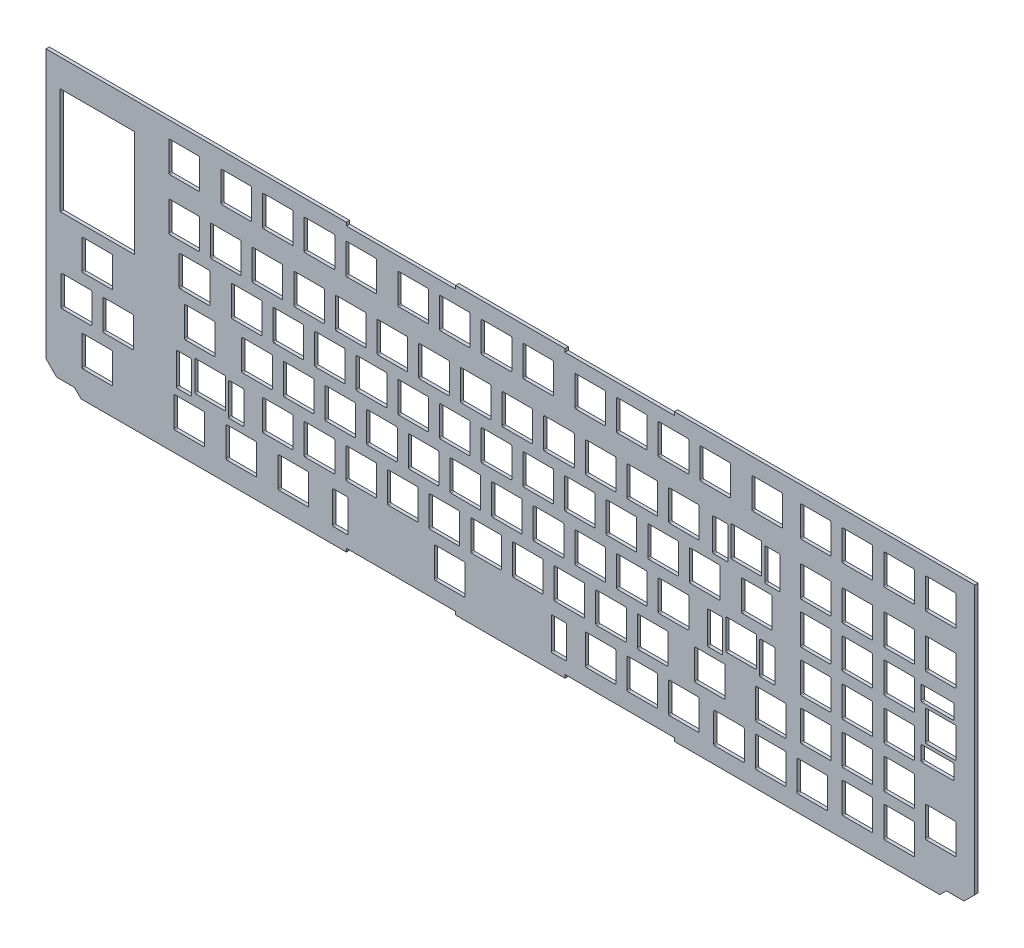
SolidWorks part; units mm, degrees
ref_plane "Přední rovina" through (0, 0, 0) normal (0, 0, 1) x (1, 0, 0)
ref_plane "Horní rovina" through (0, 0, 0) normal (0, 1, 0) x (1, 0, 0)
ref_plane "Pravá rovina" through (0, 0, 0) normal (1, 0, 0) x (0, 0, -1)
sketch "Model" plane through (0, 0, 0) normal (0, 0, 1) x (1, 0, 0)
  line L0 (53.8256, -2.525) -> (66.8256, -2.525)
  line L1 (53.8256, -16.525) -> (66.8256, -16.525)
  line L2 (53.3256, -3.025) -> (53.3256, -16.025)
  line L3 (67.3256, -3.025) -> (67.3256, -16.025)
  line L4 (77.6381, -2.525) -> (90.6381, -2.525)
  line L5 (77.6381, -16.525) -> (90.6381, -16.525)
  line L6 (77.1381, -3.025) -> (77.1381, -16.025)
  line L7 (91.1381, -3.025) -> (91.1381, -16.025)
  line L8 (96.6881, -2.525) -> (109.6881, -2.525)
  line L9 (96.6881, -16.525) -> (109.6881, -16.525)
  line L10 (96.1881, -3.025) -> (96.1881, -16.025)
  line L11 (110.1881, -3.025) -> (110.1881, -16.025)
  line L12 (115.7381, -2.525) -> (128.7381, -2.525)
  line L13 (115.7381, -16.525) -> (128.7381, -16.525)
  line L14 (115.2381, -3.025) -> (115.2381, -16.025)
  line L15 (129.2381, -3.025) -> (129.2381, -16.025)
  line L16 (134.7881, -2.525) -> (147.7881, -2.525)
  line L17 (134.7881, -16.525) -> (147.7881, -16.525)
  line L18 (134.2881, -3.025) -> (134.2881, -16.025)
  line L19 (148.2881, -3.025) -> (148.2881, -16.025)
  line L20 (158.6006, -2.525) -> (171.6006, -2.525)
  line L21 (158.6006, -16.525) -> (171.6006, -16.525)
  line L22 (158.1006, -3.025) -> (158.1006, -16.025)
  line L23 (172.1006, -3.025) -> (172.1006, -16.025)
  line L24 (177.6506, -2.525) -> (190.6506, -2.525)
  line L25 (177.6506, -16.525) -> (190.6506, -16.525)
  line L26 (177.1506, -3.025) -> (177.1506, -16.025)
  line L27 (191.1506, -3.025) -> (191.1506, -16.025)
  line L28 (196.7006, -2.525) -> (209.7006, -2.525)
  line L29 (196.7006, -16.525) -> (209.7006, -16.525)
  line L30 (196.2006, -3.025) -> (196.2006, -16.025)
  line L31 (210.2006, -3.025) -> (210.2006, -16.025)
  line L32 (215.7506, -2.525) -> (228.7506, -2.525)
  line L33 (215.7506, -16.525) -> (228.7506, -16.525)
  line L34 (215.2506, -3.025) -> (215.2506, -16.025)
  line L35 (229.2506, -3.025) -> (229.2506, -16.025)
  line L36 (239.5631, -2.525) -> (252.5631, -2.525)
  line L37 (239.5631, -16.525) -> (252.5631, -16.525)
  line L38 (239.0631, -3.025) -> (239.0631, -16.025)
  line L39 (253.0631, -3.025) -> (253.0631, -16.025)
  line L40 (258.6131, -2.525) -> (271.6131, -2.525)
  line L41 (258.6131, -16.525) -> (271.6131, -16.525)
  line L42 (258.1131, -3.025) -> (258.1131, -16.025)
  line L43 (272.1131, -3.025) -> (272.1131, -16.025)
  line L44 (277.6631, -2.525) -> (290.6631, -2.525)
  line L45 (277.6631, -16.525) -> (290.6631, -16.525)
  line L46 (277.1631, -3.025) -> (277.1631, -16.025)
  line L47 (291.1631, -3.025) -> (291.1631, -16.025)
  line L48 (296.7131, -2.525) -> (309.7131, -2.525)
  line L49 (296.7131, -16.525) -> (309.7131, -16.525)
  line L50 (296.2131, -3.025) -> (296.2131, -16.025)
  line L51 (310.2131, -3.025) -> (310.2131, -16.025)
  line L52 (320.5256, -2.525) -> (333.5256, -2.525)
  line L53 (320.5256, -16.525) -> (333.5256, -16.525)
  line L54 (320.0256, -3.025) -> (320.0256, -16.025)
  line L55 (334.0256, -3.025) -> (334.0256, -16.025)
  line L56 (342.7513, -2.525) -> (355.7513, -2.525)
  line L57 (342.7513, -16.525) -> (355.7513, -16.525)
  line L58 (342.2513, -3.025) -> (342.2513, -16.025)
  line L59 (356.2513, -3.025) -> (356.2513, -16.025)
  line L60 (361.8013, -2.525) -> (374.8013, -2.525)
  line L61 (361.8013, -16.525) -> (374.8013, -16.525)
  line L62 (361.3013, -3.025) -> (361.3013, -16.025)
  line L63 (375.3013, -3.025) -> (375.3013, -16.025)
  line L64 (380.8513, -2.525) -> (393.8513, -2.525)
  line L65 (380.8513, -16.525) -> (393.8513, -16.525)
  line L66 (380.3513, -3.025) -> (380.3513, -16.025)
  line L67 (394.3513, -3.025) -> (394.3513, -16.025)
  line L68 (399.9013, -2.525) -> (412.9013, -2.525)
  line L69 (399.9013, -16.525) -> (412.9013, -16.525)
  line L70 (399.4013, -3.025) -> (399.4013, -16.025)
  line L71 (413.4013, -3.025) -> (413.4013, -16.025)
  line L72 (53.8256, -26.3375) -> (66.8256, -26.3375)
  line L73 (53.8256, -40.3375) -> (66.8256, -40.3375)
  line L74 (53.3256, -26.8375) -> (53.3256, -39.8375)
  line L75 (67.3256, -26.8375) -> (67.3256, -39.8375)
  line L76 (72.8756, -26.3375) -> (85.8756, -26.3375)
  line L77 (72.8756, -40.3375) -> (85.8756, -40.3375)
  line L78 (72.3756, -26.8375) -> (72.3756, -39.8375)
  line L79 (86.3756, -26.8375) -> (86.3756, -39.8375)
  line L80 (91.9256, -26.3375) -> (104.9256, -26.3375)
  line L81 (91.9256, -40.3375) -> (104.9256, -40.3375)
  line L82 (91.4256, -26.8375) -> (91.4256, -39.8375)
  line L83 (105.4256, -26.8375) -> (105.4256, -39.8375)
  line L84 (110.9756, -26.3375) -> (123.9756, -26.3375)
  line L85 (110.9756, -40.3375) -> (123.9756, -40.3375)
  line L86 (110.4756, -26.8375) -> (110.4756, -39.8375)
  line L87 (124.4756, -26.8375) -> (124.4756, -39.8375)
  line L88 (130.0256, -26.3375) -> (143.0256, -26.3375)
  line L89 (130.0256, -40.3375) -> (143.0256, -40.3375)
  line L90 (129.5256, -26.8375) -> (129.5256, -39.8375)
  line L91 (143.5256, -26.8375) -> (143.5256, -39.8375)
  line L92 (149.0756, -26.3375) -> (162.0756, -26.3375)
  line L93 (149.0756, -40.3375) -> (162.0756, -40.3375)
  line L94 (148.5756, -26.8375) -> (148.5756, -39.8375)
  line L95 (162.5756, -26.8375) -> (162.5756, -39.8375)
  line L96 (168.1256, -26.3375) -> (181.1256, -26.3375)
  line L97 (168.1256, -40.3375) -> (181.1256, -40.3375)
  line L98 (167.6256, -26.8375) -> (167.6256, -39.8375)
  line L99 (181.6256, -26.8375) -> (181.6256, -39.8375)
  line L100 (187.1756, -26.3375) -> (200.1756, -26.3375)
  line L101 (187.1756, -40.3375) -> (200.1756, -40.3375)
  line L102 (186.6756, -26.8375) -> (186.6756, -39.8375)
  line L103 (200.6756, -26.8375) -> (200.6756, -39.8375)
  line L104 (206.2256, -26.3375) -> (219.2256, -26.3375)
  line L105 (206.2256, -40.3375) -> (219.2256, -40.3375)
  line L106 (205.7256, -26.8375) -> (205.7256, -39.8375)
  line L107 (219.7256, -26.8375) -> (219.7256, -39.8375)
  line L108 (225.2756, -26.3375) -> (238.2756, -26.3375)
  line L109 (225.2756, -40.3375) -> (238.2756, -40.3375)
  line L110 (224.7756, -26.8375) -> (224.7756, -39.8375)
  line L111 (238.7756, -26.8375) -> (238.7756, -39.8375)
  line L112 (244.3256, -26.3375) -> (257.3256, -26.3375)
  line L113 (244.3256, -40.3375) -> (257.3256, -40.3375)
  line L114 (243.8256, -26.8375) -> (243.8256, -39.8375)
  line L115 (257.8256, -26.8375) -> (257.8256, -39.8375)
  line L116 (263.3756, -26.3375) -> (276.3756, -26.3375)
  line L117 (263.3756, -40.3375) -> (276.3756, -40.3375)
  line L118 (262.8756, -26.8375) -> (262.8756, -39.8375)
  line L119 (276.8756, -26.8375) -> (276.8756, -39.8375)
  line L120 (282.4256, -26.3375) -> (295.4256, -26.3375)
  line L121 (282.4256, -40.3375) -> (295.4256, -40.3375)
  line L122 (281.9256, -26.8375) -> (281.9256, -39.8375)
  line L123 (295.9256, -26.8375) -> (295.9256, -39.8375)
  line L124 (311.0006, -26.3375) -> (324.0006, -26.3375)
  line L125 (311.0006, -40.3375) -> (324.0006, -40.3375)
  line L126 (310.5006, -26.8375) -> (310.5006, -39.8375)
  line L127 (324.5006, -26.8375) -> (324.5006, -39.8375)
  line L128 (302.5626, -27.3375) -> (308.5626, -27.3375)
  line L129 (302.5626, -42.3375) -> (308.5626, -42.3375)
  line L130 (302.0626, -27.8375) -> (302.0626, -41.8375)
  line L131 (309.0626, -27.8375) -> (309.0626, -41.8375)
  line L132 (326.4386, -27.3375) -> (332.4386, -27.3375)
  line L133 (326.4386, -42.3375) -> (332.4386, -42.3375)
  line L134 (325.9386, -27.8375) -> (325.9386, -41.8375)
  line L135 (332.9386, -27.8375) -> (332.9386, -41.8375)
  line L136 (342.7513, -26.3375) -> (355.7513, -26.3375)
  line L137 (342.7513, -40.3375) -> (355.7513, -40.3375)
  line L138 (342.2513, -26.8375) -> (342.2513, -39.8375)
  line L139 (356.2513, -26.8375) -> (356.2513, -39.8375)
  line L140 (361.8013, -26.3375) -> (374.8013, -26.3375)
  line L141 (361.8013, -40.3375) -> (374.8013, -40.3375)
  line L142 (361.3013, -26.8375) -> (361.3013, -39.8375)
  line L143 (375.3013, -26.8375) -> (375.3013, -39.8375)
  line L144 (380.8513, -26.3375) -> (393.8513, -26.3375)
  line L145 (380.8513, -40.3375) -> (393.8513, -40.3375)
  line L146 (380.3513, -26.8375) -> (380.3513, -39.8375)
  line L147 (394.3513, -26.8375) -> (394.3513, -39.8375)
  line L148 (399.9013, -26.3375) -> (412.9013, -26.3375)
  line L149 (399.9013, -40.3375) -> (412.9013, -40.3375)
  line L150 (399.4013, -26.8375) -> (399.4013, -39.8375)
  line L151 (413.4013, -26.8375) -> (413.4013, -39.8375)
  line L152 (58.5881, -45.3875) -> (71.5881, -45.3875)
  line L153 (58.5881, -59.3875) -> (71.5881, -59.3875)
  line L154 (58.0881, -45.8875) -> (58.0881, -58.8875)
  line L155 (72.0881, -45.8875) -> (72.0881, -58.8875)
  line L156 (82.4006, -45.3875) -> (95.4006, -45.3875)
  line L157 (82.4006, -59.3875) -> (95.4006, -59.3875)
  line L158 (81.9006, -45.8875) -> (81.9006, -58.8875)
  line L159 (95.9006, -45.8875) -> (95.9006, -58.8875)
  line L160 (101.4506, -45.3875) -> (114.4506, -45.3875)
  line L161 (101.4506, -59.3875) -> (114.4506, -59.3875)
  line L162 (100.9506, -45.8875) -> (100.9506, -58.8875)
  line L163 (114.9506, -45.8875) -> (114.9506, -58.8875)
  line L164 (120.5006, -45.3875) -> (133.5006, -45.3875)
  line L165 (120.5006, -59.3875) -> (133.5006, -59.3875)
  line L166 (120.0006, -45.8875) -> (120.0006, -58.8875)
  line L167 (134.0006, -45.8875) -> (134.0006, -58.8875)
  line L168 (139.5506, -45.3875) -> (152.5506, -45.3875)
  line L169 (139.5506, -59.3875) -> (152.5506, -59.3875)
  line L170 (139.0506, -45.8875) -> (139.0506, -58.8875)
  line L171 (153.0506, -45.8875) -> (153.0506, -58.8875)
  line L172 (158.6006, -45.3875) -> (171.6006, -45.3875)
  line L173 (158.6006, -59.3875) -> (171.6006, -59.3875)
  line L174 (158.1006, -45.8875) -> (158.1006, -58.8875)
  line L175 (172.1006, -45.8875) -> (172.1006, -58.8875)
  line L176 (177.6506, -45.3875) -> (190.6506, -45.3875)
  line L177 (177.6506, -59.3875) -> (190.6506, -59.3875)
  line L178 (177.1506, -45.8875) -> (177.1506, -58.8875)
  line L179 (191.1506, -45.8875) -> (191.1506, -58.8875)
  line L180 (196.7006, -45.3875) -> (209.7006, -45.3875)
  line L181 (196.7006, -59.3875) -> (209.7006, -59.3875)
  line L182 (196.2006, -45.8875) -> (196.2006, -58.8875)
  line L183 (210.2006, -45.8875) -> (210.2006, -58.8875)
  line L184 (215.7506, -45.3875) -> (228.7506, -45.3875)
  line L185 (215.7506, -59.3875) -> (228.7506, -59.3875)
  line L186 (215.2506, -45.8875) -> (215.2506, -58.8875)
  line L187 (229.2506, -45.8875) -> (229.2506, -58.8875)
  line L188 (234.8006, -45.3875) -> (247.8006, -45.3875)
  line L189 (234.8006, -59.3875) -> (247.8006, -59.3875)
  line L190 (234.3006, -45.8875) -> (234.3006, -58.8875)
  line L191 (248.3006, -45.8875) -> (248.3006, -58.8875)
  line L192 (253.8506, -45.3875) -> (266.8506, -45.3875)
  line L193 (253.8506, -59.3875) -> (266.8506, -59.3875)
  line L194 (253.3506, -45.8875) -> (253.3506, -58.8875)
  line L195 (267.3506, -45.8875) -> (267.3506, -58.8875)
  line L196 (272.9006, -45.3875) -> (285.9006, -45.3875)
  line L197 (272.9006, -59.3875) -> (285.9006, -59.3875)
  line L198 (272.4006, -45.8875) -> (272.4006, -58.8875)
  line L199 (286.4006, -45.8875) -> (286.4006, -58.8875)
  line L200 (291.9506, -45.3875) -> (304.9506, -45.3875)
  line L201 (291.9506, -59.3875) -> (304.9506, -59.3875)
  line L202 (291.4506, -45.8875) -> (291.4506, -58.8875)
  line L203 (305.4506, -45.8875) -> (305.4506, -58.8875)
  line L204 (315.7631, -45.3875) -> (328.7631, -45.3875)
  line L205 (315.7631, -59.3875) -> (328.7631, -59.3875)
  line L206 (315.2631, -45.8875) -> (315.2631, -58.8875)
  line L207 (329.2631, -45.8875) -> (329.2631, -58.8875)
  line L208 (342.7513, -45.3875) -> (355.7513, -45.3875)
  line L209 (342.7513, -59.3875) -> (355.7513, -59.3875)
  line L210 (342.2513, -45.8875) -> (342.2513, -58.8875)
  line L211 (356.2513, -45.8875) -> (356.2513, -58.8875)
  line L212 (361.8013, -45.3875) -> (374.8013, -45.3875)
  line L213 (361.8013, -59.3875) -> (374.8013, -59.3875)
  line L214 (361.3013, -45.8875) -> (361.3013, -58.8875)
  line L215 (375.3013, -45.8875) -> (375.3013, -58.8875)
  line L216 (380.8513, -45.3875) -> (393.8513, -45.3875)
  line L217 (380.8513, -59.3875) -> (393.8513, -59.3875)
  line L218 (380.3513, -45.8875) -> (380.3513, -58.8875)
  line L219 (394.3513, -45.8875) -> (394.3513, -58.8875)
  line L220 (413.4013, -55.4125) -> (413.4013, -68.4125)
  line L221 (399.4013, -55.4125) -> (399.4013, -68.4125)
  line L222 (412.9013, -54.9125) -> (399.9013, -54.9125)
  line L223 (412.9013, -68.9125) -> (399.9013, -68.9125)
  line L224 (412.4013, -46.9745) -> (412.4013, -52.9745)
  line L225 (397.4013, -46.9745) -> (397.4013, -52.9745)
  line L226 (411.9013, -46.4745) -> (397.9013, -46.4745)
  line L227 (411.9013, -53.4745) -> (397.9013, -53.4745)
  line L228 (412.4013, -70.8505) -> (412.4013, -76.8505)
  line L229 (397.4013, -70.8505) -> (397.4013, -76.8505)
  line L230 (411.9013, -70.3505) -> (397.9013, -70.3505)
  line L231 (411.9013, -77.3505) -> (397.9013, -77.3505)
  line L232 (14.1369, -61.2619) -> (27.1369, -61.2619)
  line L233 (14.1369, -75.2619) -> (27.1369, -75.2619)
  line L234 (13.6369, -61.7619) -> (13.6369, -74.7619)
  line L235 (27.6369, -61.7619) -> (27.6369, -74.7619)
  line L236 (60.9694, -64.4375) -> (73.9694, -64.4375)
  line L237 (60.9694, -78.4375) -> (73.9694, -78.4375)
  line L238 (60.4694, -64.9375) -> (60.4694, -77.9375)
  line L239 (74.4694, -64.9375) -> (74.4694, -77.9375)
  line L240 (87.1631, -64.4375) -> (100.1631, -64.4375)
  line L241 (87.1631, -78.4375) -> (100.1631, -78.4375)
  line L242 (86.6631, -64.9375) -> (86.6631, -77.9375)
  line L243 (100.6631, -64.9375) -> (100.6631, -77.9375)
  line L244 (106.2131, -64.4375) -> (119.2131, -64.4375)
  line L245 (106.2131, -78.4375) -> (119.2131, -78.4375)
  line L246 (105.7131, -64.9375) -> (105.7131, -77.9375)
  line L247 (119.7131, -64.9375) -> (119.7131, -77.9375)
  line L248 (125.2631, -64.4375) -> (138.2631, -64.4375)
  line L249 (125.2631, -78.4375) -> (138.2631, -78.4375)
  line L250 (124.7631, -64.9375) -> (124.7631, -77.9375)
  line L251 (138.7631, -64.9375) -> (138.7631, -77.9375)
  line L252 (144.3131, -64.4375) -> (157.3131, -64.4375)
  line L253 (144.3131, -78.4375) -> (157.3131, -78.4375)
  line L254 (143.8131, -64.9375) -> (143.8131, -77.9375)
  line L255 (157.8131, -64.9375) -> (157.8131, -77.9375)
  line L256 (163.3631, -64.4375) -> (176.3631, -64.4375)
  line L257 (163.3631, -78.4375) -> (176.3631, -78.4375)
  line L258 (162.8631, -64.9375) -> (162.8631, -77.9375)
  line L259 (176.8631, -64.9375) -> (176.8631, -77.9375)
  line L260 (182.4131, -64.4375) -> (195.4131, -64.4375)
  line L261 (182.4131, -78.4375) -> (195.4131, -78.4375)
  line L262 (181.9131, -64.9375) -> (181.9131, -77.9375)
  line L263 (195.9131, -64.9375) -> (195.9131, -77.9375)
  line L264 (201.4631, -64.4375) -> (214.4631, -64.4375)
  line L265 (201.4631, -78.4375) -> (214.4631, -78.4375)
  line L266 (200.9631, -64.9375) -> (200.9631, -77.9375)
  line L267 (214.9631, -64.9375) -> (214.9631, -77.9375)
  line L268 (220.5131, -64.4375) -> (233.5131, -64.4375)
  line L269 (220.5131, -78.4375) -> (233.5131, -78.4375)
  line L270 (220.0131, -64.9375) -> (220.0131, -77.9375)
  line L271 (234.0131, -64.9375) -> (234.0131, -77.9375)
  line L272 (239.5631, -64.4375) -> (252.5631, -64.4375)
  line L273 (239.5631, -78.4375) -> (252.5631, -78.4375)
  line L274 (239.0631, -64.9375) -> (239.0631, -77.9375)
  line L275 (253.0631, -64.9375) -> (253.0631, -77.9375)
  line L276 (258.6131, -64.4375) -> (271.6131, -64.4375)
  line L277 (258.6131, -78.4375) -> (271.6131, -78.4375)
  line L278 (258.1131, -64.9375) -> (258.1131, -77.9375)
  line L279 (272.1131, -64.9375) -> (272.1131, -77.9375)
  line L280 (277.6631, -64.4375) -> (290.6631, -64.4375)
  line L281 (277.6631, -78.4375) -> (290.6631, -78.4375)
  line L282 (277.1631, -64.9375) -> (277.1631, -77.9375)
  line L283 (291.1631, -64.9375) -> (291.1631, -77.9375)
  line L284 (308.6194, -64.4375) -> (321.6194, -64.4375)
  line L285 (308.6194, -78.4375) -> (321.6194, -78.4375)
  line L286 (308.1194, -64.9375) -> (308.1194, -77.9375)
  line L287 (322.1194, -64.9375) -> (322.1194, -77.9375)
  line L288 (300.1814, -65.4375) -> (306.1814, -65.4375)
  line L289 (300.1814, -80.4375) -> (306.1814, -80.4375)
  line L290 (299.6814, -65.9375) -> (299.6814, -79.9375)
  line L291 (306.6814, -65.9375) -> (306.6814, -79.9375)
  line L292 (324.0574, -65.4375) -> (330.0574, -65.4375)
  line L293 (324.0574, -80.4375) -> (330.0574, -80.4375)
  line L294 (323.5574, -65.9375) -> (323.5574, -79.9375)
  line L295 (330.5574, -65.9375) -> (330.5574, -79.9375)
  line L296 (342.7513, -64.4375) -> (355.7513, -64.4375)
  line L297 (342.7513, -78.4375) -> (355.7513, -78.4375)
  line L298 (342.2513, -64.9375) -> (342.2513, -77.9375)
  line L299 (356.2513, -64.9375) -> (356.2513, -77.9375)
  line L300 (361.8013, -64.4375) -> (374.8013, -64.4375)
  line L301 (361.8013, -78.4375) -> (374.8013, -78.4375)
  line L302 (361.3013, -64.9375) -> (361.3013, -77.9375)
  line L303 (375.3013, -64.9375) -> (375.3013, -77.9375)
  line L304 (380.8513, -64.4375) -> (393.8513, -64.4375)
  line L305 (380.8513, -78.4375) -> (393.8513, -78.4375)
  line L306 (380.3513, -64.9375) -> (380.3513, -77.9375)
  line L307 (394.3513, -64.9375) -> (394.3513, -77.9375)
  line L308 (4.6119, -80.3119) -> (17.6119, -80.3119)
  line L309 (4.6119, -94.3119) -> (17.6119, -94.3119)
  line L310 (4.1119, -80.8119) -> (4.1119, -93.8119)
  line L311 (18.1119, -80.8119) -> (18.1119, -93.8119)
  line L312 (23.6619, -80.3119) -> (36.6619, -80.3119)
  line L313 (23.6619, -94.3119) -> (36.6619, -94.3119)
  line L314 (23.1619, -80.8119) -> (23.1619, -93.8119)
  line L315 (37.1619, -80.8119) -> (37.1619, -93.8119)
  line L316 (65.7319, -83.4875) -> (78.7319, -83.4875)
  line L317 (65.7319, -97.4875) -> (78.7319, -97.4875)
  line L318 (65.2319, -83.9875) -> (65.2319, -96.9875)
  line L319 (79.2319, -83.9875) -> (79.2319, -96.9875)
  line L320 (57.2939, -84.4875) -> (63.2939, -84.4875)
  line L321 (57.2939, -99.4875) -> (63.2939, -99.4875)
  line L322 (56.7939, -84.9875) -> (56.7939, -98.9875)
  line L323 (63.7939, -84.9875) -> (63.7939, -98.9875)
  line L324 (81.1699, -84.4875) -> (87.1699, -84.4875)
  line L325 (81.1699, -99.4875) -> (87.1699, -99.4875)
  line L326 (80.6699, -84.9875) -> (80.6699, -98.9875)
  line L327 (87.6699, -84.9875) -> (87.6699, -98.9875)
  line L328 (96.6881, -83.4875) -> (109.6881, -83.4875)
  line L329 (96.6881, -97.4875) -> (109.6881, -97.4875)
  line L330 (96.1881, -83.9875) -> (96.1881, -96.9875)
  line L331 (110.1881, -83.9875) -> (110.1881, -96.9875)
  line L332 (115.7381, -83.4875) -> (128.7381, -83.4875)
  line L333 (115.7381, -97.4875) -> (128.7381, -97.4875)
  line L334 (115.2381, -83.9875) -> (115.2381, -96.9875)
  line L335 (129.2381, -83.9875) -> (129.2381, -96.9875)
  line L336 (134.7881, -83.4875) -> (147.7881, -83.4875)
  line L337 (134.7881, -97.4875) -> (147.7881, -97.4875)
  line L338 (134.2881, -83.9875) -> (134.2881, -96.9875)
  line L339 (148.2881, -83.9875) -> (148.2881, -96.9875)
  line L340 (153.8381, -83.4875) -> (166.8381, -83.4875)
  line L341 (153.8381, -97.4875) -> (166.8381, -97.4875)
  line L342 (153.3381, -83.9875) -> (153.3381, -96.9875)
  line L343 (167.3381, -83.9875) -> (167.3381, -96.9875)
  line L344 (172.8881, -83.4875) -> (185.8881, -83.4875)
  line L345 (172.8881, -97.4875) -> (185.8881, -97.4875)
  line L346 (172.3881, -83.9875) -> (172.3881, -96.9875)
  line L347 (186.3881, -83.9875) -> (186.3881, -96.9875)
  line L348 (191.9381, -83.4875) -> (204.9381, -83.4875)
  line L349 (191.9381, -97.4875) -> (204.9381, -97.4875)
  line L350 (191.4381, -83.9875) -> (191.4381, -96.9875)
  line L351 (205.4381, -83.9875) -> (205.4381, -96.9875)
  line L352 (210.9881, -83.4875) -> (223.9881, -83.4875)
  line L353 (210.9881, -97.4875) -> (223.9881, -97.4875)
  line L354 (210.4881, -83.9875) -> (210.4881, -96.9875)
  line L355 (224.4881, -83.9875) -> (224.4881, -96.9875)
  line L356 (230.0381, -83.4875) -> (243.0381, -83.4875)
  line L357 (230.0381, -97.4875) -> (243.0381, -97.4875)
  line L358 (229.5381, -83.9875) -> (229.5381, -96.9875)
  line L359 (243.5381, -83.9875) -> (243.5381, -96.9875)
  line L360 (249.0881, -83.4875) -> (262.0881, -83.4875)
  line L361 (249.0881, -97.4875) -> (262.0881, -97.4875)
  line L362 (248.5881, -83.9875) -> (248.5881, -96.9875)
  line L363 (262.5881, -83.9875) -> (262.5881, -96.9875)
  line L364 (268.1381, -83.4875) -> (281.1381, -83.4875)
  line L365 (268.1381, -97.4875) -> (281.1381, -97.4875)
  line L366 (267.6381, -83.9875) -> (267.6381, -96.9875)
  line L367 (281.6381, -83.9875) -> (281.6381, -96.9875)
  line L368 (294.3319, -83.4875) -> (307.3319, -83.4875)
  line L369 (294.3319, -97.4875) -> (307.3319, -97.4875)
  line L370 (293.8319, -83.9875) -> (293.8319, -96.9875)
  line L371 (307.8319, -83.9875) -> (307.8319, -96.9875)
  line L372 (342.7513, -83.4875) -> (355.7513, -83.4875)
  line L373 (342.7513, -97.4875) -> (355.7513, -97.4875)
  line L374 (342.2513, -83.9875) -> (342.2513, -96.9875)
  line L375 (356.2513, -83.9875) -> (356.2513, -96.9875)
  line L376 (361.8013, -83.4875) -> (374.8013, -83.4875)
  line L377 (361.8013, -97.4875) -> (374.8013, -97.4875)
  line L378 (361.3013, -83.9875) -> (361.3013, -96.9875)
  line L379 (375.3013, -83.9875) -> (375.3013, -96.9875)
  line L380 (380.8513, -83.4875) -> (393.8513, -83.4875)
  line L381 (380.8513, -97.4875) -> (393.8513, -97.4875)
  line L382 (380.3513, -83.9875) -> (380.3513, -96.9875)
  line L383 (394.3513, -83.9875) -> (394.3513, -96.9875)
  line L384 (413.4013, -93.5125) -> (413.4013, -106.5125)
  line L385 (399.4013, -93.5125) -> (399.4013, -106.5125)
  line L386 (412.9013, -93.0125) -> (399.9013, -93.0125)
  line L387 (412.9013, -107.0125) -> (399.9013, -107.0125)
  line L396 (322.1125, -85.0744) -> (335.1125, -85.0744)
  line L397 (322.1125, -99.0744) -> (335.1125, -99.0744)
  line L398 (321.6125, -85.5744) -> (321.6125, -98.5744)
  line L399 (335.6125, -85.5744) -> (335.6125, -98.5744)
  line L400 (14.1369, -99.3619) -> (27.1369, -99.3619)
  line L401 (14.1369, -113.3619) -> (27.1369, -113.3619)
  line L402 (13.6369, -99.8619) -> (13.6369, -112.8619)
  line L403 (27.6369, -99.8619) -> (27.6369, -112.8619)
  line L404 (56.2069, -102.5375) -> (69.2069, -102.5375)
  line L405 (56.2069, -116.5375) -> (69.2069, -116.5375)
  line L406 (55.7069, -103.0375) -> (55.7069, -116.0375)
  line L407 (69.7069, -103.0375) -> (69.7069, -116.0375)
  line L408 (80.0194, -102.5375) -> (93.0194, -102.5375)
  line L409 (80.0194, -116.5375) -> (93.0194, -116.5375)
  line L410 (79.5194, -103.0375) -> (79.5194, -116.0375)
  line L411 (93.5194, -103.0375) -> (93.5194, -116.0375)
  line L412 (103.8319, -102.5375) -> (116.8319, -102.5375)
  line L413 (103.8319, -116.5375) -> (116.8319, -116.5375)
  line L414 (103.3319, -103.0375) -> (103.3319, -116.0375)
  line L415 (117.3319, -103.0375) -> (117.3319, -116.0375)
  line L416 (175.2694, -102.5375) -> (188.2694, -102.5375)
  line L417 (175.2694, -116.5375) -> (188.2694, -116.5375)
  line L418 (174.7694, -103.0375) -> (174.7694, -116.0375)
  line L419 (188.7694, -103.0375) -> (188.7694, -116.0375)
  line L420 (128.7694, -103.5375) -> (134.7694, -103.5375)
  line L421 (128.7694, -118.5375) -> (134.7694, -118.5375)
  line L422 (128.2694, -104.0375) -> (128.2694, -118.0375)
  line L423 (135.2694, -104.0375) -> (135.2694, -118.0375)
  line L424 (228.7694, -103.5375) -> (234.7694, -103.5375)
  line L425 (228.7694, -118.5375) -> (234.7694, -118.5375)
  line L426 (228.2694, -104.0375) -> (228.2694, -118.0375)
  line L427 (235.2694, -104.0375) -> (235.2694, -118.0375)
  line L428 (244.3256, -102.5375) -> (257.3256, -102.5375)
  line L429 (244.3256, -116.5375) -> (257.3256, -116.5375)
  line L430 (243.8256, -103.0375) -> (243.8256, -116.0375)
  line L431 (257.8256, -103.0375) -> (257.8256, -116.0375)
  line L432 (263.3756, -102.5375) -> (276.3756, -102.5375)
  line L433 (263.3756, -116.5375) -> (276.3756, -116.5375)
  line L434 (262.8756, -103.0375) -> (262.8756, -116.0375)
  line L435 (276.8756, -103.0375) -> (276.8756, -116.0375)
  line L436 (282.4256, -102.5375) -> (295.4256, -102.5375)
  line L437 (282.4256, -116.5375) -> (295.4256, -116.5375)
  line L438 (281.9256, -103.0375) -> (281.9256, -116.0375)
  line L439 (295.9256, -103.0375) -> (295.9256, -116.0375)
  line L440 (361.8013, -102.5375) -> (374.8013, -102.5375)
  line L441 (361.8013, -116.5375) -> (374.8013, -116.5375)
  line L442 (361.3013, -103.0375) -> (361.3013, -116.0375)
  line L443 (375.3013, -103.0375) -> (375.3013, -116.0375)
  line L444 (380.8513, -102.5375) -> (393.8513, -102.5375)
  line L445 (380.8513, -116.5375) -> (393.8513, -116.5375)
  line L446 (380.3513, -103.0375) -> (380.3513, -116.0375)
  line L447 (394.3513, -103.0375) -> (394.3513, -116.0375)
  line L448 (303.0625, -104.1244) -> (316.0625, -104.1244)
  line L449 (303.0625, -118.1244) -> (316.0625, -118.1244)
  line L450 (302.5625, -104.6244) -> (302.5625, -117.6244)
  line L451 (316.5625, -104.6244) -> (316.5625, -117.6244)
  line L452 (322.1125, -104.1244) -> (335.1125, -104.1244)
  line L453 (322.1125, -118.1244) -> (335.1125, -118.1244)
  line L454 (321.6125, -104.6244) -> (321.6125, -117.6244)
  line L455 (335.6125, -104.6244) -> (335.6125, -117.6244)
  line L456 (341.1625, -104.1244) -> (354.1625, -104.1244)
  line L457 (341.1625, -118.1244) -> (354.1625, -118.1244)
  line L458 (340.6625, -104.6244) -> (340.6625, -117.6244)
  line L459 (354.6625, -104.6244) -> (354.6625, -117.6244)
  line L460 (1.5869, -120.6494) -> (417.5131, -120.6494)
  line L461 (1.5869, 0) -> (417.5131, 0)
  line L462 (1.5869, -120.6494) -> (1.5869, 0)
  line L463 (417.5131, -120.6494) -> (417.5131, 0)
  arc A0 (53.8256, -2.525) -> (53.3256, -3.025) centre (53.8256, -3.025) ccw
  arc A1 (67.3256, -3.025) -> (66.8256, -2.525) centre (66.8256, -3.025) ccw
  arc A2 (53.3256, -16.025) -> (53.8256, -16.525) centre (53.8256, -16.025) ccw
  arc A3 (66.8256, -16.525) -> (67.3256, -16.025) centre (66.8256, -16.025) ccw
  arc A4 (77.6381, -2.525) -> (77.1381, -3.025) centre (77.6381, -3.025) ccw
  arc A5 (91.1381, -3.025) -> (90.6381, -2.525) centre (90.6381, -3.025) ccw
  arc A6 (77.1381, -16.025) -> (77.6381, -16.525) centre (77.6381, -16.025) ccw
  arc A7 (90.6381, -16.525) -> (91.1381, -16.025) centre (90.6381, -16.025) ccw
  arc A8 (96.6881, -2.525) -> (96.1881, -3.025) centre (96.6881, -3.025) ccw
  arc A9 (110.1881, -3.025) -> (109.6881, -2.525) centre (109.6881, -3.025) ccw
  arc A10 (96.1881, -16.025) -> (96.6881, -16.525) centre (96.6881, -16.025) ccw
  arc A11 (109.6881, -16.525) -> (110.1881, -16.025) centre (109.6881, -16.025) ccw
  arc A12 (115.7381, -2.525) -> (115.2381, -3.025) centre (115.7381, -3.025) ccw
  arc A13 (129.2381, -3.025) -> (128.7381, -2.525) centre (128.7381, -3.025) ccw
  arc A14 (115.2381, -16.025) -> (115.7381, -16.525) centre (115.7381, -16.025) ccw
  arc A15 (128.7381, -16.525) -> (129.2381, -16.025) centre (128.7381, -16.025) ccw
  arc A16 (134.7881, -2.525) -> (134.2881, -3.025) centre (134.7881, -3.025) ccw
  arc A17 (148.2881, -3.025) -> (147.7881, -2.525) centre (147.7881, -3.025) ccw
  arc A18 (134.2881, -16.025) -> (134.7881, -16.525) centre (134.7881, -16.025) ccw
  arc A19 (147.7881, -16.525) -> (148.2881, -16.025) centre (147.7881, -16.025) ccw
  arc A20 (158.6006, -2.525) -> (158.1006, -3.025) centre (158.6006, -3.025) ccw
  arc A21 (172.1006, -3.025) -> (171.6006, -2.525) centre (171.6006, -3.025) ccw
  arc A22 (158.1006, -16.025) -> (158.6006, -16.525) centre (158.6006, -16.025) ccw
  arc A23 (171.6006, -16.525) -> (172.1006, -16.025) centre (171.6006, -16.025) ccw
  arc A24 (177.6506, -2.525) -> (177.1506, -3.025) centre (177.6506, -3.025) ccw
  arc A25 (191.1506, -3.025) -> (190.6506, -2.525) centre (190.6506, -3.025) ccw
  arc A26 (177.1506, -16.025) -> (177.6506, -16.525) centre (177.6506, -16.025) ccw
  arc A27 (190.6506, -16.525) -> (191.1506, -16.025) centre (190.6506, -16.025) ccw
  arc A28 (196.7006, -2.525) -> (196.2006, -3.025) centre (196.7006, -3.025) ccw
  arc A29 (210.2006, -3.025) -> (209.7006, -2.525) centre (209.7006, -3.025) ccw
  arc A30 (196.2006, -16.025) -> (196.7006, -16.525) centre (196.7006, -16.025) ccw
  arc A31 (209.7006, -16.525) -> (210.2006, -16.025) centre (209.7006, -16.025) ccw
  arc A32 (215.7506, -2.525) -> (215.2506, -3.025) centre (215.7506, -3.025) ccw
  arc A33 (229.2506, -3.025) -> (228.7506, -2.525) centre (228.7506, -3.025) ccw
  arc A34 (215.2506, -16.025) -> (215.7506, -16.525) centre (215.7506, -16.025) ccw
  arc A35 (228.7506, -16.525) -> (229.2506, -16.025) centre (228.7506, -16.025) ccw
  arc A36 (239.5631, -2.525) -> (239.0631, -3.025) centre (239.5631, -3.025) ccw
  arc A37 (253.0631, -3.025) -> (252.5631, -2.525) centre (252.5631, -3.025) ccw
  arc A38 (239.0631, -16.025) -> (239.5631, -16.525) centre (239.5631, -16.025) ccw
  arc A39 (252.5631, -16.525) -> (253.0631, -16.025) centre (252.5631, -16.025) ccw
  arc A40 (258.6131, -2.525) -> (258.1131, -3.025) centre (258.6131, -3.025) ccw
  arc A41 (272.1131, -3.025) -> (271.6131, -2.525) centre (271.6131, -3.025) ccw
  arc A42 (258.1131, -16.025) -> (258.6131, -16.525) centre (258.6131, -16.025) ccw
  arc A43 (271.6131, -16.525) -> (272.1131, -16.025) centre (271.6131, -16.025) ccw
  arc A44 (277.6631, -2.525) -> (277.1631, -3.025) centre (277.6631, -3.025) ccw
  arc A45 (291.1631, -3.025) -> (290.6631, -2.525) centre (290.6631, -3.025) ccw
  arc A46 (277.1631, -16.025) -> (277.6631, -16.525) centre (277.6631, -16.025) ccw
  arc A47 (290.6631, -16.525) -> (291.1631, -16.025) centre (290.6631, -16.025) ccw
  arc A48 (296.7131, -2.525) -> (296.2131, -3.025) centre (296.7131, -3.025) ccw
  arc A49 (310.2131, -3.025) -> (309.7131, -2.525) centre (309.7131, -3.025) ccw
  arc A50 (296.2131, -16.025) -> (296.7131, -16.525) centre (296.7131, -16.025) ccw
  arc A51 (309.7131, -16.525) -> (310.2131, -16.025) centre (309.7131, -16.025) ccw
  arc A52 (320.5256, -2.525) -> (320.0256, -3.025) centre (320.5256, -3.025) ccw
  arc A53 (334.0256, -3.025) -> (333.5256, -2.525) centre (333.5256, -3.025) ccw
  arc A54 (320.0256, -16.025) -> (320.5256, -16.525) centre (320.5256, -16.025) ccw
  arc A55 (333.5256, -16.525) -> (334.0256, -16.025) centre (333.5256, -16.025) ccw
  arc A56 (342.7513, -2.525) -> (342.2513, -3.025) centre (342.7513, -3.025) ccw
  arc A57 (356.2513, -3.025) -> (355.7513, -2.525) centre (355.7513, -3.025) ccw
  arc A58 (342.2513, -16.025) -> (342.7513, -16.525) centre (342.7513, -16.025) ccw
  arc A59 (355.7513, -16.525) -> (356.2513, -16.025) centre (355.7513, -16.025) ccw
  arc A60 (361.8013, -2.525) -> (361.3013, -3.025) centre (361.8013, -3.025) ccw
  arc A61 (375.3013, -3.025) -> (374.8013, -2.525) centre (374.8013, -3.025) ccw
  arc A62 (361.3013, -16.025) -> (361.8013, -16.525) centre (361.8013, -16.025) ccw
  arc A63 (374.8013, -16.525) -> (375.3013, -16.025) centre (374.8013, -16.025) ccw
  arc A64 (380.8513, -2.525) -> (380.3513, -3.025) centre (380.8513, -3.025) ccw
  arc A65 (394.3513, -3.025) -> (393.8513, -2.525) centre (393.8513, -3.025) ccw
  arc A66 (380.3513, -16.025) -> (380.8513, -16.525) centre (380.8513, -16.025) ccw
  arc A67 (393.8513, -16.525) -> (394.3513, -16.025) centre (393.8513, -16.025) ccw
  arc A68 (399.9013, -2.525) -> (399.4013, -3.025) centre (399.9013, -3.025) ccw
  arc A69 (413.4013, -3.025) -> (412.9013, -2.525) centre (412.9013, -3.025) ccw
  arc A70 (399.4013, -16.025) -> (399.9013, -16.525) centre (399.9013, -16.025) ccw
  arc A71 (412.9013, -16.525) -> (413.4013, -16.025) centre (412.9013, -16.025) ccw
  arc A72 (53.8256, -26.3375) -> (53.3256, -26.8375) centre (53.8256, -26.8375) ccw
  arc A73 (67.3256, -26.8375) -> (66.8256, -26.3375) centre (66.8256, -26.8375) ccw
  arc A74 (53.3256, -39.8375) -> (53.8256, -40.3375) centre (53.8256, -39.8375) ccw
  arc A75 (66.8256, -40.3375) -> (67.3256, -39.8375) centre (66.8256, -39.8375) ccw
  arc A76 (72.8756, -26.3375) -> (72.3756, -26.8375) centre (72.8756, -26.8375) ccw
  arc A77 (86.3756, -26.8375) -> (85.8756, -26.3375) centre (85.8756, -26.8375) ccw
  arc A78 (72.3756, -39.8375) -> (72.8756, -40.3375) centre (72.8756, -39.8375) ccw
  arc A79 (85.8756, -40.3375) -> (86.3756, -39.8375) centre (85.8756, -39.8375) ccw
  arc A80 (91.9256, -26.3375) -> (91.4256, -26.8375) centre (91.9256, -26.8375) ccw
  arc A81 (105.4256, -26.8375) -> (104.9256, -26.3375) centre (104.9256, -26.8375) ccw
  arc A82 (91.4256, -39.8375) -> (91.9256, -40.3375) centre (91.9256, -39.8375) ccw
  arc A83 (104.9256, -40.3375) -> (105.4256, -39.8375) centre (104.9256, -39.8375) ccw
  arc A84 (110.9756, -26.3375) -> (110.4756, -26.8375) centre (110.9756, -26.8375) ccw
  arc A85 (124.4756, -26.8375) -> (123.9756, -26.3375) centre (123.9756, -26.8375) ccw
  arc A86 (110.4756, -39.8375) -> (110.9756, -40.3375) centre (110.9756, -39.8375) ccw
  arc A87 (123.9756, -40.3375) -> (124.4756, -39.8375) centre (123.9756, -39.8375) ccw
  arc A88 (130.0256, -26.3375) -> (129.5256, -26.8375) centre (130.0256, -26.8375) ccw
  arc A89 (143.5256, -26.8375) -> (143.0256, -26.3375) centre (143.0256, -26.8375) ccw
  arc A90 (129.5256, -39.8375) -> (130.0256, -40.3375) centre (130.0256, -39.8375) ccw
  arc A91 (143.0256, -40.3375) -> (143.5256, -39.8375) centre (143.0256, -39.8375) ccw
  arc A92 (149.0756, -26.3375) -> (148.5756, -26.8375) centre (149.0756, -26.8375) ccw
  arc A93 (162.5756, -26.8375) -> (162.0756, -26.3375) centre (162.0756, -26.8375) ccw
  arc A94 (148.5756, -39.8375) -> (149.0756, -40.3375) centre (149.0756, -39.8375) ccw
  arc A95 (162.0756, -40.3375) -> (162.5756, -39.8375) centre (162.0756, -39.8375) ccw
  arc A96 (168.1256, -26.3375) -> (167.6256, -26.8375) centre (168.1256, -26.8375) ccw
  arc A97 (181.6256, -26.8375) -> (181.1256, -26.3375) centre (181.1256, -26.8375) ccw
  arc A98 (167.6256, -39.8375) -> (168.1256, -40.3375) centre (168.1256, -39.8375) ccw
  arc A99 (181.1256, -40.3375) -> (181.6256, -39.8375) centre (181.1256, -39.8375) ccw
  arc A100 (187.1756, -26.3375) -> (186.6756, -26.8375) centre (187.1756, -26.8375) ccw
  arc A101 (200.6756, -26.8375) -> (200.1756, -26.3375) centre (200.1756, -26.8375) ccw
  arc A102 (186.6756, -39.8375) -> (187.1756, -40.3375) centre (187.1756, -39.8375) ccw
  arc A103 (200.1756, -40.3375) -> (200.6756, -39.8375) centre (200.1756, -39.8375) ccw
  arc A104 (206.2256, -26.3375) -> (205.7256, -26.8375) centre (206.2256, -26.8375) ccw
  arc A105 (219.7256, -26.8375) -> (219.2256, -26.3375) centre (219.2256, -26.8375) ccw
  arc A106 (205.7256, -39.8375) -> (206.2256, -40.3375) centre (206.2256, -39.8375) ccw
  arc A107 (219.2256, -40.3375) -> (219.7256, -39.8375) centre (219.2256, -39.8375) ccw
  arc A108 (225.2756, -26.3375) -> (224.7756, -26.8375) centre (225.2756, -26.8375) ccw
  arc A109 (238.7756, -26.8375) -> (238.2756, -26.3375) centre (238.2756, -26.8375) ccw
  arc A110 (224.7756, -39.8375) -> (225.2756, -40.3375) centre (225.2756, -39.8375) ccw
  arc A111 (238.2756, -40.3375) -> (238.7756, -39.8375) centre (238.2756, -39.8375) ccw
  arc A112 (244.3256, -26.3375) -> (243.8256, -26.8375) centre (244.3256, -26.8375) ccw
  arc A113 (257.8256, -26.8375) -> (257.3256, -26.3375) centre (257.3256, -26.8375) ccw
  arc A114 (243.8256, -39.8375) -> (244.3256, -40.3375) centre (244.3256, -39.8375) ccw
  arc A115 (257.3256, -40.3375) -> (257.8256, -39.8375) centre (257.3256, -39.8375) ccw
  arc A116 (263.3756, -26.3375) -> (262.8756, -26.8375) centre (263.3756, -26.8375) ccw
  arc A117 (276.8756, -26.8375) -> (276.3756, -26.3375) centre (276.3756, -26.8375) ccw
  arc A118 (262.8756, -39.8375) -> (263.3756, -40.3375) centre (263.3756, -39.8375) ccw
  arc A119 (276.3756, -40.3375) -> (276.8756, -39.8375) centre (276.3756, -39.8375) ccw
  arc A120 (282.4256, -26.3375) -> (281.9256, -26.8375) centre (282.4256, -26.8375) ccw
  arc A121 (295.9256, -26.8375) -> (295.4256, -26.3375) centre (295.4256, -26.8375) ccw
  arc A122 (281.9256, -39.8375) -> (282.4256, -40.3375) centre (282.4256, -39.8375) ccw
  arc A123 (295.4256, -40.3375) -> (295.9256, -39.8375) centre (295.4256, -39.8375) ccw
  arc A124 (311.0006, -26.3375) -> (310.5006, -26.8375) centre (311.0006, -26.8375) ccw
  arc A125 (324.5006, -26.8375) -> (324.0006, -26.3375) centre (324.0006, -26.8375) ccw
  arc A126 (310.5006, -39.8375) -> (311.0006, -40.3375) centre (311.0006, -39.8375) ccw
  arc A127 (324.0006, -40.3375) -> (324.5006, -39.8375) centre (324.0006, -39.8375) ccw
  arc A128 (302.5626, -27.3375) -> (302.0626, -27.8375) centre (302.5626, -27.8375) ccw
  arc A129 (309.0626, -27.8375) -> (308.5626, -27.3375) centre (308.5626, -27.8375) ccw
  arc A130 (302.0626, -41.8375) -> (302.5626, -42.3375) centre (302.5626, -41.8375) ccw
  arc A131 (308.5626, -42.3375) -> (309.0626, -41.8375) centre (308.5626, -41.8375) ccw
  arc A132 (326.4386, -27.3375) -> (325.9386, -27.8375) centre (326.4386, -27.8375) ccw
  arc A133 (332.9386, -27.8375) -> (332.4386, -27.3375) centre (332.4386, -27.8375) ccw
  arc A134 (325.9386, -41.8375) -> (326.4386, -42.3375) centre (326.4386, -41.8375) ccw
  arc A135 (332.4386, -42.3375) -> (332.9386, -41.8375) centre (332.4386, -41.8375) ccw
  arc A136 (342.7513, -26.3375) -> (342.2513, -26.8375) centre (342.7513, -26.8375) ccw
  arc A137 (356.2513, -26.8375) -> (355.7513, -26.3375) centre (355.7513, -26.8375) ccw
  arc A138 (342.2513, -39.8375) -> (342.7513, -40.3375) centre (342.7513, -39.8375) ccw
  arc A139 (355.7513, -40.3375) -> (356.2513, -39.8375) centre (355.7513, -39.8375) ccw
  arc A140 (361.8013, -26.3375) -> (361.3013, -26.8375) centre (361.8013, -26.8375) ccw
  arc A141 (375.3013, -26.8375) -> (374.8013, -26.3375) centre (374.8013, -26.8375) ccw
  arc A142 (361.3013, -39.8375) -> (361.8013, -40.3375) centre (361.8013, -39.8375) ccw
  arc A143 (374.8013, -40.3375) -> (375.3013, -39.8375) centre (374.8013, -39.8375) ccw
  arc A144 (380.8513, -26.3375) -> (380.3513, -26.8375) centre (380.8513, -26.8375) ccw
  arc A145 (394.3513, -26.8375) -> (393.8513, -26.3375) centre (393.8513, -26.8375) ccw
  arc A146 (380.3513, -39.8375) -> (380.8513, -40.3375) centre (380.8513, -39.8375) ccw
  arc A147 (393.8513, -40.3375) -> (394.3513, -39.8375) centre (393.8513, -39.8375) ccw
  arc A148 (399.9013, -26.3375) -> (399.4013, -26.8375) centre (399.9013, -26.8375) ccw
  arc A149 (413.4013, -26.8375) -> (412.9013, -26.3375) centre (412.9013, -26.8375) ccw
  arc A150 (399.4013, -39.8375) -> (399.9013, -40.3375) centre (399.9013, -39.8375) ccw
  arc A151 (412.9013, -40.3375) -> (413.4013, -39.8375) centre (412.9013, -39.8375) ccw
  arc A152 (58.5881, -45.3875) -> (58.0881, -45.8875) centre (58.5881, -45.8875) ccw
  arc A153 (72.0881, -45.8875) -> (71.5881, -45.3875) centre (71.5881, -45.8875) ccw
  arc A154 (58.0881, -58.8875) -> (58.5881, -59.3875) centre (58.5881, -58.8875) ccw
  arc A155 (71.5881, -59.3875) -> (72.0881, -58.8875) centre (71.5881, -58.8875) ccw
  arc A156 (82.4006, -45.3875) -> (81.9006, -45.8875) centre (82.4006, -45.8875) ccw
  arc A157 (95.9006, -45.8875) -> (95.4006, -45.3875) centre (95.4006, -45.8875) ccw
  arc A158 (81.9006, -58.8875) -> (82.4006, -59.3875) centre (82.4006, -58.8875) ccw
  arc A159 (95.4006, -59.3875) -> (95.9006, -58.8875) centre (95.4006, -58.8875) ccw
  arc A160 (101.4506, -45.3875) -> (100.9506, -45.8875) centre (101.4506, -45.8875) ccw
  arc A161 (114.9506, -45.8875) -> (114.4506, -45.3875) centre (114.4506, -45.8875) ccw
  arc A162 (100.9506, -58.8875) -> (101.4506, -59.3875) centre (101.4506, -58.8875) ccw
  arc A163 (114.4506, -59.3875) -> (114.9506, -58.8875) centre (114.4506, -58.8875) ccw
  arc A164 (120.5006, -45.3875) -> (120.0006, -45.8875) centre (120.5006, -45.8875) ccw
  arc A165 (134.0006, -45.8875) -> (133.5006, -45.3875) centre (133.5006, -45.8875) ccw
  arc A166 (120.0006, -58.8875) -> (120.5006, -59.3875) centre (120.5006, -58.8875) ccw
  arc A167 (133.5006, -59.3875) -> (134.0006, -58.8875) centre (133.5006, -58.8875) ccw
  arc A168 (139.5506, -45.3875) -> (139.0506, -45.8875) centre (139.5506, -45.8875) ccw
  arc A169 (153.0506, -45.8875) -> (152.5506, -45.3875) centre (152.5506, -45.8875) ccw
  arc A170 (139.0506, -58.8875) -> (139.5506, -59.3875) centre (139.5506, -58.8875) ccw
  arc A171 (152.5506, -59.3875) -> (153.0506, -58.8875) centre (152.5506, -58.8875) ccw
  arc A172 (158.6006, -45.3875) -> (158.1006, -45.8875) centre (158.6006, -45.8875) ccw
  arc A173 (172.1006, -45.8875) -> (171.6006, -45.3875) centre (171.6006, -45.8875) ccw
  arc A174 (158.1006, -58.8875) -> (158.6006, -59.3875) centre (158.6006, -58.8875) ccw
  arc A175 (171.6006, -59.3875) -> (172.1006, -58.8875) centre (171.6006, -58.8875) ccw
  arc A176 (177.6506, -45.3875) -> (177.1506, -45.8875) centre (177.6506, -45.8875) ccw
  arc A177 (191.1506, -45.8875) -> (190.6506, -45.3875) centre (190.6506, -45.8875) ccw
  arc A178 (177.1506, -58.8875) -> (177.6506, -59.3875) centre (177.6506, -58.8875) ccw
  arc A179 (190.6506, -59.3875) -> (191.1506, -58.8875) centre (190.6506, -58.8875) ccw
  arc A180 (196.7006, -45.3875) -> (196.2006, -45.8875) centre (196.7006, -45.8875) ccw
  arc A181 (210.2006, -45.8875) -> (209.7006, -45.3875) centre (209.7006, -45.8875) ccw
  arc A182 (196.2006, -58.8875) -> (196.7006, -59.3875) centre (196.7006, -58.8875) ccw
  arc A183 (209.7006, -59.3875) -> (210.2006, -58.8875) centre (209.7006, -58.8875) ccw
  arc A184 (215.7506, -45.3875) -> (215.2506, -45.8875) centre (215.7506, -45.8875) ccw
  arc A185 (229.2506, -45.8875) -> (228.7506, -45.3875) centre (228.7506, -45.8875) ccw
  arc A186 (215.2506, -58.8875) -> (215.7506, -59.3875) centre (215.7506, -58.8875) ccw
  arc A187 (228.7506, -59.3875) -> (229.2506, -58.8875) centre (228.7506, -58.8875) ccw
  arc A188 (234.8006, -45.3875) -> (234.3006, -45.8875) centre (234.8006, -45.8875) ccw
  arc A189 (248.3006, -45.8875) -> (247.8006, -45.3875) centre (247.8006, -45.8875) ccw
  arc A190 (234.3006, -58.8875) -> (234.8006, -59.3875) centre (234.8006, -58.8875) ccw
  arc A191 (247.8006, -59.3875) -> (248.3006, -58.8875) centre (247.8006, -58.8875) ccw
  arc A192 (253.8506, -45.3875) -> (253.3506, -45.8875) centre (253.8506, -45.8875) ccw
  arc A193 (267.3506, -45.8875) -> (266.8506, -45.3875) centre (266.8506, -45.8875) ccw
  arc A194 (253.3506, -58.8875) -> (253.8506, -59.3875) centre (253.8506, -58.8875) ccw
  arc A195 (266.8506, -59.3875) -> (267.3506, -58.8875) centre (266.8506, -58.8875) ccw
  arc A196 (272.9006, -45.3875) -> (272.4006, -45.8875) centre (272.9006, -45.8875) ccw
  arc A197 (286.4006, -45.8875) -> (285.9006, -45.3875) centre (285.9006, -45.8875) ccw
  arc A198 (272.4006, -58.8875) -> (272.9006, -59.3875) centre (272.9006, -58.8875) ccw
  arc A199 (285.9006, -59.3875) -> (286.4006, -58.8875) centre (285.9006, -58.8875) ccw
  arc A200 (291.9506, -45.3875) -> (291.4506, -45.8875) centre (291.9506, -45.8875) ccw
  arc A201 (305.4506, -45.8875) -> (304.9506, -45.3875) centre (304.9506, -45.8875) ccw
  arc A202 (291.4506, -58.8875) -> (291.9506, -59.3875) centre (291.9506, -58.8875) ccw
  arc A203 (304.9506, -59.3875) -> (305.4506, -58.8875) centre (304.9506, -58.8875) ccw
  arc A204 (315.7631, -45.3875) -> (315.2631, -45.8875) centre (315.7631, -45.8875) ccw
  arc A205 (329.2631, -45.8875) -> (328.7631, -45.3875) centre (328.7631, -45.8875) ccw
  arc A206 (315.2631, -58.8875) -> (315.7631, -59.3875) centre (315.7631, -58.8875) ccw
  arc A207 (328.7631, -59.3875) -> (329.2631, -58.8875) centre (328.7631, -58.8875) ccw
  arc A208 (342.7513, -45.3875) -> (342.2513, -45.8875) centre (342.7513, -45.8875) ccw
  arc A209 (356.2513, -45.8875) -> (355.7513, -45.3875) centre (355.7513, -45.8875) ccw
  arc A210 (342.2513, -58.8875) -> (342.7513, -59.3875) centre (342.7513, -58.8875) ccw
  arc A211 (355.7513, -59.3875) -> (356.2513, -58.8875) centre (355.7513, -58.8875) ccw
  arc A212 (361.8013, -45.3875) -> (361.3013, -45.8875) centre (361.8013, -45.8875) ccw
  arc A213 (375.3013, -45.8875) -> (374.8013, -45.3875) centre (374.8013, -45.8875) ccw
  arc A214 (361.3013, -58.8875) -> (361.8013, -59.3875) centre (361.8013, -58.8875) ccw
  arc A215 (374.8013, -59.3875) -> (375.3013, -58.8875) centre (374.8013, -58.8875) ccw
  arc A216 (380.8513, -45.3875) -> (380.3513, -45.8875) centre (380.8513, -45.8875) ccw
  arc A217 (394.3513, -45.8875) -> (393.8513, -45.3875) centre (393.8513, -45.8875) ccw
  arc A218 (380.3513, -58.8875) -> (380.8513, -59.3875) centre (380.8513, -58.8875) ccw
  arc A219 (393.8513, -59.3875) -> (394.3513, -58.8875) centre (393.8513, -58.8875) ccw
  arc A220 (413.4013, -55.4125) -> (412.9013, -54.9125) centre (412.9013, -55.4125) ccw
  arc A221 (412.9013, -68.9125) -> (413.4013, -68.4125) centre (412.9013, -68.4125) ccw
  arc A222 (399.9013, -54.9125) -> (399.4013, -55.4125) centre (399.9013, -55.4125) ccw
  arc A223 (399.4013, -68.4125) -> (399.9013, -68.9125) centre (399.9013, -68.4125) ccw
  arc A224 (412.4013, -46.9745) -> (411.9013, -46.4745) centre (411.9013, -46.9745) ccw
  arc A225 (411.9013, -53.4745) -> (412.4013, -52.9745) centre (411.9013, -52.9745) ccw
  arc A226 (397.9013, -46.4745) -> (397.4013, -46.9745) centre (397.9013, -46.9745) ccw
  arc A227 (397.4013, -52.9745) -> (397.9013, -53.4745) centre (397.9013, -52.9745) ccw
  arc A228 (412.4013, -70.8505) -> (411.9013, -70.3505) centre (411.9013, -70.8505) ccw
  arc A229 (411.9013, -77.3505) -> (412.4013, -76.8505) centre (411.9013, -76.8505) ccw
  arc A230 (397.9013, -70.3505) -> (397.4013, -70.8505) centre (397.9013, -70.8505) ccw
  arc A231 (397.4013, -76.8505) -> (397.9013, -77.3505) centre (397.9013, -76.8505) ccw
  arc A232 (14.1369, -61.2619) -> (13.6369, -61.7619) centre (14.1369, -61.7619) ccw
  arc A233 (27.6369, -61.7619) -> (27.1369, -61.2619) centre (27.1369, -61.7619) ccw
  arc A234 (13.6369, -74.7619) -> (14.1369, -75.2619) centre (14.1369, -74.7619) ccw
  arc A235 (27.1369, -75.2619) -> (27.6369, -74.7619) centre (27.1369, -74.7619) ccw
  arc A236 (60.9694, -64.4375) -> (60.4694, -64.9375) centre (60.9694, -64.9375) ccw
  arc A237 (74.4694, -64.9375) -> (73.9694, -64.4375) centre (73.9694, -64.9375) ccw
  arc A238 (60.4694, -77.9375) -> (60.9694, -78.4375) centre (60.9694, -77.9375) ccw
  arc A239 (73.9694, -78.4375) -> (74.4694, -77.9375) centre (73.9694, -77.9375) ccw
  arc A240 (87.1631, -64.4375) -> (86.6631, -64.9375) centre (87.1631, -64.9375) ccw
  arc A241 (100.6631, -64.9375) -> (100.1631, -64.4375) centre (100.1631, -64.9375) ccw
  arc A242 (86.6631, -77.9375) -> (87.1631, -78.4375) centre (87.1631, -77.9375) ccw
  arc A243 (100.1631, -78.4375) -> (100.6631, -77.9375) centre (100.1631, -77.9375) ccw
  arc A244 (106.2131, -64.4375) -> (105.7131, -64.9375) centre (106.2131, -64.9375) ccw
  arc A245 (119.7131, -64.9375) -> (119.2131, -64.4375) centre (119.2131, -64.9375) ccw
  arc A246 (105.7131, -77.9375) -> (106.2131, -78.4375) centre (106.2131, -77.9375) ccw
  arc A247 (119.2131, -78.4375) -> (119.7131, -77.9375) centre (119.2131, -77.9375) ccw
  arc A248 (125.2631, -64.4375) -> (124.7631, -64.9375) centre (125.2631, -64.9375) ccw
  arc A249 (138.7631, -64.9375) -> (138.2631, -64.4375) centre (138.2631, -64.9375) ccw
  arc A250 (124.7631, -77.9375) -> (125.2631, -78.4375) centre (125.2631, -77.9375) ccw
  arc A251 (138.2631, -78.4375) -> (138.7631, -77.9375) centre (138.2631, -77.9375) ccw
  arc A252 (144.3131, -64.4375) -> (143.8131, -64.9375) centre (144.3131, -64.9375) ccw
  arc A253 (157.8131, -64.9375) -> (157.3131, -64.4375) centre (157.3131, -64.9375) ccw
  arc A254 (143.8131, -77.9375) -> (144.3131, -78.4375) centre (144.3131, -77.9375) ccw
  arc A255 (157.3131, -78.4375) -> (157.8131, -77.9375) centre (157.3131, -77.9375) ccw
  arc A256 (163.3631, -64.4375) -> (162.8631, -64.9375) centre (163.3631, -64.9375) ccw
  arc A257 (176.8631, -64.9375) -> (176.3631, -64.4375) centre (176.3631, -64.9375) ccw
  arc A258 (162.8631, -77.9375) -> (163.3631, -78.4375) centre (163.3631, -77.9375) ccw
  arc A259 (176.3631, -78.4375) -> (176.8631, -77.9375) centre (176.3631, -77.9375) ccw
  arc A260 (182.4131, -64.4375) -> (181.9131, -64.9375) centre (182.4131, -64.9375) ccw
  arc A261 (195.9131, -64.9375) -> (195.4131, -64.4375) centre (195.4131, -64.9375) ccw
  arc A262 (181.9131, -77.9375) -> (182.4131, -78.4375) centre (182.4131, -77.9375) ccw
  arc A263 (195.4131, -78.4375) -> (195.9131, -77.9375) centre (195.4131, -77.9375) ccw
  arc A264 (201.4631, -64.4375) -> (200.9631, -64.9375) centre (201.4631, -64.9375) ccw
  arc A265 (214.9631, -64.9375) -> (214.4631, -64.4375) centre (214.4631, -64.9375) ccw
  arc A266 (200.9631, -77.9375) -> (201.4631, -78.4375) centre (201.4631, -77.9375) ccw
  arc A267 (214.4631, -78.4375) -> (214.9631, -77.9375) centre (214.4631, -77.9375) ccw
  arc A268 (220.5131, -64.4375) -> (220.0131, -64.9375) centre (220.5131, -64.9375) ccw
  arc A269 (234.0131, -64.9375) -> (233.5131, -64.4375) centre (233.5131, -64.9375) ccw
  arc A270 (220.0131, -77.9375) -> (220.5131, -78.4375) centre (220.5131, -77.9375) ccw
  arc A271 (233.5131, -78.4375) -> (234.0131, -77.9375) centre (233.5131, -77.9375) ccw
  arc A272 (239.5631, -64.4375) -> (239.0631, -64.9375) centre (239.5631, -64.9375) ccw
  arc A273 (253.0631, -64.9375) -> (252.5631, -64.4375) centre (252.5631, -64.9375) ccw
  arc A274 (239.0631, -77.9375) -> (239.5631, -78.4375) centre (239.5631, -77.9375) ccw
  arc A275 (252.5631, -78.4375) -> (253.0631, -77.9375) centre (252.5631, -77.9375) ccw
  arc A276 (258.6131, -64.4375) -> (258.1131, -64.9375) centre (258.6131, -64.9375) ccw
  arc A277 (272.1131, -64.9375) -> (271.6131, -64.4375) centre (271.6131, -64.9375) ccw
  arc A278 (258.1131, -77.9375) -> (258.6131, -78.4375) centre (258.6131, -77.9375) ccw
  arc A279 (271.6131, -78.4375) -> (272.1131, -77.9375) centre (271.6131, -77.9375) ccw
  arc A280 (277.6631, -64.4375) -> (277.1631, -64.9375) centre (277.6631, -64.9375) ccw
  arc A281 (291.1631, -64.9375) -> (290.6631, -64.4375) centre (290.6631, -64.9375) ccw
  arc A282 (277.1631, -77.9375) -> (277.6631, -78.4375) centre (277.6631, -77.9375) ccw
  arc A283 (290.6631, -78.4375) -> (291.1631, -77.9375) centre (290.6631, -77.9375) ccw
  arc A284 (308.6194, -64.4375) -> (308.1194, -64.9375) centre (308.6194, -64.9375) ccw
  arc A285 (322.1194, -64.9375) -> (321.6194, -64.4375) centre (321.6194, -64.9375) ccw
  arc A286 (308.1194, -77.9375) -> (308.6194, -78.4375) centre (308.6194, -77.9375) ccw
  arc A287 (321.6194, -78.4375) -> (322.1194, -77.9375) centre (321.6194, -77.9375) ccw
  arc A288 (300.1814, -65.4375) -> (299.6814, -65.9375) centre (300.1814, -65.9375) ccw
  arc A289 (306.6814, -65.9375) -> (306.1814, -65.4375) centre (306.1814, -65.9375) ccw
  arc A290 (299.6814, -79.9375) -> (300.1814, -80.4375) centre (300.1814, -79.9375) ccw
  arc A291 (306.1814, -80.4375) -> (306.6814, -79.9375) centre (306.1814, -79.9375) ccw
  arc A292 (324.0574, -65.4375) -> (323.5574, -65.9375) centre (324.0574, -65.9375) ccw
  arc A293 (330.5574, -65.9375) -> (330.0574, -65.4375) centre (330.0574, -65.9375) ccw
  arc A294 (323.5574, -79.9375) -> (324.0574, -80.4375) centre (324.0574, -79.9375) ccw
  arc A295 (330.0574, -80.4375) -> (330.5574, -79.9375) centre (330.0574, -79.9375) ccw
  arc A296 (342.7513, -64.4375) -> (342.2513, -64.9375) centre (342.7513, -64.9375) ccw
  arc A297 (356.2513, -64.9375) -> (355.7513, -64.4375) centre (355.7513, -64.9375) ccw
  arc A298 (342.2513, -77.9375) -> (342.7513, -78.4375) centre (342.7513, -77.9375) ccw
  arc A299 (355.7513, -78.4375) -> (356.2513, -77.9375) centre (355.7513, -77.9375) ccw
  arc A300 (361.8013, -64.4375) -> (361.3013, -64.9375) centre (361.8013, -64.9375) ccw
  arc A301 (375.3013, -64.9375) -> (374.8013, -64.4375) centre (374.8013, -64.9375) ccw
  arc A302 (361.3013, -77.9375) -> (361.8013, -78.4375) centre (361.8013, -77.9375) ccw
  arc A303 (374.8013, -78.4375) -> (375.3013, -77.9375) centre (374.8013, -77.9375) ccw
  arc A304 (380.8513, -64.4375) -> (380.3513, -64.9375) centre (380.8513, -64.9375) ccw
  arc A305 (394.3513, -64.9375) -> (393.8513, -64.4375) centre (393.8513, -64.9375) ccw
  arc A306 (380.3513, -77.9375) -> (380.8513, -78.4375) centre (380.8513, -77.9375) ccw
  arc A307 (393.8513, -78.4375) -> (394.3513, -77.9375) centre (393.8513, -77.9375) ccw
  arc A308 (4.6119, -80.3119) -> (4.1119, -80.8119) centre (4.6119, -80.8119) ccw
  arc A309 (18.1119, -80.8119) -> (17.6119, -80.3119) centre (17.6119, -80.8119) ccw
  arc A310 (4.1119, -93.8119) -> (4.6119, -94.3119) centre (4.6119, -93.8119) ccw
  arc A311 (17.6119, -94.3119) -> (18.1119, -93.8119) centre (17.6119, -93.8119) ccw
  arc A312 (23.6619, -80.3119) -> (23.1619, -80.8119) centre (23.6619, -80.8119) ccw
  arc A313 (37.1619, -80.8119) -> (36.6619, -80.3119) centre (36.6619, -80.8119) ccw
  arc A314 (23.1619, -93.8119) -> (23.6619, -94.3119) centre (23.6619, -93.8119) ccw
  arc A315 (36.6619, -94.3119) -> (37.1619, -93.8119) centre (36.6619, -93.8119) ccw
  arc A316 (65.7319, -83.4875) -> (65.2319, -83.9875) centre (65.7319, -83.9875) ccw
  arc A317 (79.2319, -83.9875) -> (78.7319, -83.4875) centre (78.7319, -83.9875) ccw
  arc A318 (65.2319, -96.9875) -> (65.7319, -97.4875) centre (65.7319, -96.9875) ccw
  arc A319 (78.7319, -97.4875) -> (79.2319, -96.9875) centre (78.7319, -96.9875) ccw
  arc A320 (57.2939, -84.4875) -> (56.7939, -84.9875) centre (57.2939, -84.9875) ccw
  arc A321 (63.7939, -84.9875) -> (63.2939, -84.4875) centre (63.2939, -84.9875) ccw
  arc A322 (56.7939, -98.9875) -> (57.2939, -99.4875) centre (57.2939, -98.9875) ccw
  arc A323 (63.2939, -99.4875) -> (63.7939, -98.9875) centre (63.2939, -98.9875) ccw
  arc A324 (81.1699, -84.4875) -> (80.6699, -84.9875) centre (81.1699, -84.9875) ccw
  arc A325 (87.6699, -84.9875) -> (87.1699, -84.4875) centre (87.1699, -84.9875) ccw
  arc A326 (80.6699, -98.9875) -> (81.1699, -99.4875) centre (81.1699, -98.9875) ccw
  arc A327 (87.1699, -99.4875) -> (87.6699, -98.9875) centre (87.1699, -98.9875) ccw
  arc A328 (96.6881, -83.4875) -> (96.1881, -83.9875) centre (96.6881, -83.9875) ccw
  arc A329 (110.1881, -83.9875) -> (109.6881, -83.4875) centre (109.6881, -83.9875) ccw
  arc A330 (96.1881, -96.9875) -> (96.6881, -97.4875) centre (96.6881, -96.9875) ccw
  arc A331 (109.6881, -97.4875) -> (110.1881, -96.9875) centre (109.6881, -96.9875) ccw
  arc A332 (115.7381, -83.4875) -> (115.2381, -83.9875) centre (115.7381, -83.9875) ccw
  arc A333 (129.2381, -83.9875) -> (128.7381, -83.4875) centre (128.7381, -83.9875) ccw
  arc A334 (115.2381, -96.9875) -> (115.7381, -97.4875) centre (115.7381, -96.9875) ccw
  arc A335 (128.7381, -97.4875) -> (129.2381, -96.9875) centre (128.7381, -96.9875) ccw
  arc A336 (134.7881, -83.4875) -> (134.2881, -83.9875) centre (134.7881, -83.9875) ccw
  arc A337 (148.2881, -83.9875) -> (147.7881, -83.4875) centre (147.7881, -83.9875) ccw
  arc A338 (134.2881, -96.9875) -> (134.7881, -97.4875) centre (134.7881, -96.9875) ccw
  arc A339 (147.7881, -97.4875) -> (148.2881, -96.9875) centre (147.7881, -96.9875) ccw
  arc A340 (153.8381, -83.4875) -> (153.3381, -83.9875) centre (153.8381, -83.9875) ccw
  arc A341 (167.3381, -83.9875) -> (166.8381, -83.4875) centre (166.8381, -83.9875) ccw
  arc A342 (153.3381, -96.9875) -> (153.8381, -97.4875) centre (153.8381, -96.9875) ccw
  arc A343 (166.8381, -97.4875) -> (167.3381, -96.9875) centre (166.8381, -96.9875) ccw
  arc A344 (172.8881, -83.4875) -> (172.3881, -83.9875) centre (172.8881, -83.9875) ccw
  arc A345 (186.3881, -83.9875) -> (185.8881, -83.4875) centre (185.8881, -83.9875) ccw
  arc A346 (172.3881, -96.9875) -> (172.8881, -97.4875) centre (172.8881, -96.9875) ccw
  arc A347 (185.8881, -97.4875) -> (186.3881, -96.9875) centre (185.8881, -96.9875) ccw
  arc A348 (191.9381, -83.4875) -> (191.4381, -83.9875) centre (191.9381, -83.9875) ccw
  arc A349 (205.4381, -83.9875) -> (204.9381, -83.4875) centre (204.9381, -83.9875) ccw
  arc A350 (191.4381, -96.9875) -> (191.9381, -97.4875) centre (191.9381, -96.9875) ccw
  arc A351 (204.9381, -97.4875) -> (205.4381, -96.9875) centre (204.9381, -96.9875) ccw
  arc A352 (210.9881, -83.4875) -> (210.4881, -83.9875) centre (210.9881, -83.9875) ccw
  arc A353 (224.4881, -83.9875) -> (223.9881, -83.4875) centre (223.9881, -83.9875) ccw
  arc A354 (210.4881, -96.9875) -> (210.9881, -97.4875) centre (210.9881, -96.9875) ccw
  arc A355 (223.9881, -97.4875) -> (224.4881, -96.9875) centre (223.9881, -96.9875) ccw
  arc A356 (230.0381, -83.4875) -> (229.5381, -83.9875) centre (230.0381, -83.9875) ccw
  arc A357 (243.5381, -83.9875) -> (243.0381, -83.4875) centre (243.0381, -83.9875) ccw
  arc A358 (229.5381, -96.9875) -> (230.0381, -97.4875) centre (230.0381, -96.9875) ccw
  arc A359 (243.0381, -97.4875) -> (243.5381, -96.9875) centre (243.0381, -96.9875) ccw
  arc A360 (249.0881, -83.4875) -> (248.5881, -83.9875) centre (249.0881, -83.9875) ccw
  arc A361 (262.5881, -83.9875) -> (262.0881, -83.4875) centre (262.0881, -83.9875) ccw
  arc A362 (248.5881, -96.9875) -> (249.0881, -97.4875) centre (249.0881, -96.9875) ccw
  arc A363 (262.0881, -97.4875) -> (262.5881, -96.9875) centre (262.0881, -96.9875) ccw
  arc A364 (268.1381, -83.4875) -> (267.6381, -83.9875) centre (268.1381, -83.9875) ccw
  arc A365 (281.6381, -83.9875) -> (281.1381, -83.4875) centre (281.1381, -83.9875) ccw
  arc A366 (267.6381, -96.9875) -> (268.1381, -97.4875) centre (268.1381, -96.9875) ccw
  arc A367 (281.1381, -97.4875) -> (281.6381, -96.9875) centre (281.1381, -96.9875) ccw
  arc A368 (294.3319, -83.4875) -> (293.8319, -83.9875) centre (294.3319, -83.9875) ccw
  arc A369 (307.8319, -83.9875) -> (307.3319, -83.4875) centre (307.3319, -83.9875) ccw
  arc A370 (293.8319, -96.9875) -> (294.3319, -97.4875) centre (294.3319, -96.9875) ccw
  arc A371 (307.3319, -97.4875) -> (307.8319, -96.9875) centre (307.3319, -96.9875) ccw
  arc A372 (342.7513, -83.4875) -> (342.2513, -83.9875) centre (342.7513, -83.9875) ccw
  arc A373 (356.2513, -83.9875) -> (355.7513, -83.4875) centre (355.7513, -83.9875) ccw
  arc A374 (342.2513, -96.9875) -> (342.7513, -97.4875) centre (342.7513, -96.9875) ccw
  arc A375 (355.7513, -97.4875) -> (356.2513, -96.9875) centre (355.7513, -96.9875) ccw
  arc A376 (361.8013, -83.4875) -> (361.3013, -83.9875) centre (361.8013, -83.9875) ccw
  arc A377 (375.3013, -83.9875) -> (374.8013, -83.4875) centre (374.8013, -83.9875) ccw
  arc A378 (361.3013, -96.9875) -> (361.8013, -97.4875) centre (361.8013, -96.9875) ccw
  arc A379 (374.8013, -97.4875) -> (375.3013, -96.9875) centre (374.8013, -96.9875) ccw
  arc A380 (380.8513, -83.4875) -> (380.3513, -83.9875) centre (380.8513, -83.9875) ccw
  arc A381 (394.3513, -83.9875) -> (393.8513, -83.4875) centre (393.8513, -83.9875) ccw
  arc A382 (380.3513, -96.9875) -> (380.8513, -97.4875) centre (380.8513, -96.9875) ccw
  arc A383 (393.8513, -97.4875) -> (394.3513, -96.9875) centre (393.8513, -96.9875) ccw
  arc A384 (413.4013, -93.5125) -> (412.9013, -93.0125) centre (412.9013, -93.5125) ccw
  arc A385 (412.9013, -107.0125) -> (413.4013, -106.5125) centre (412.9013, -106.5125) ccw
  arc A386 (399.9013, -93.0125) -> (399.4013, -93.5125) centre (399.9013, -93.5125) ccw
  arc A387 (399.4013, -106.5125) -> (399.9013, -107.0125) centre (399.9013, -106.5125) ccw
  arc A396 (322.1125, -85.0744) -> (321.6125, -85.5744) centre (322.1125, -85.5744) ccw
  arc A397 (335.6125, -85.5744) -> (335.1125, -85.0744) centre (335.1125, -85.5744) ccw
  arc A398 (321.6125, -98.5744) -> (322.1125, -99.0744) centre (322.1125, -98.5744) ccw
  arc A399 (335.1125, -99.0744) -> (335.6125, -98.5744) centre (335.1125, -98.5744) ccw
  arc A400 (14.1369, -99.3619) -> (13.6369, -99.8619) centre (14.1369, -99.8619) ccw
  arc A401 (27.6369, -99.8619) -> (27.1369, -99.3619) centre (27.1369, -99.8619) ccw
  arc A402 (13.6369, -112.8619) -> (14.1369, -113.3619) centre (14.1369, -112.8619) ccw
  arc A403 (27.1369, -113.3619) -> (27.6369, -112.8619) centre (27.1369, -112.8619) ccw
  arc A404 (56.2069, -102.5375) -> (55.7069, -103.0375) centre (56.2069, -103.0375) ccw
  arc A405 (69.7069, -103.0375) -> (69.2069, -102.5375) centre (69.2069, -103.0375) ccw
  arc A406 (55.7069, -116.0375) -> (56.2069, -116.5375) centre (56.2069, -116.0375) ccw
  arc A407 (69.2069, -116.5375) -> (69.7069, -116.0375) centre (69.2069, -116.0375) ccw
  arc A408 (80.0194, -102.5375) -> (79.5194, -103.0375) centre (80.0194, -103.0375) ccw
  arc A409 (93.5194, -103.0375) -> (93.0194, -102.5375) centre (93.0194, -103.0375) ccw
  arc A410 (79.5194, -116.0375) -> (80.0194, -116.5375) centre (80.0194, -116.0375) ccw
  arc A411 (93.0194, -116.5375) -> (93.5194, -116.0375) centre (93.0194, -116.0375) ccw
  arc A412 (103.8319, -102.5375) -> (103.3319, -103.0375) centre (103.8319, -103.0375) ccw
  arc A413 (117.3319, -103.0375) -> (116.8319, -102.5375) centre (116.8319, -103.0375) ccw
  arc A414 (103.3319, -116.0375) -> (103.8319, -116.5375) centre (103.8319, -116.0375) ccw
  arc A415 (116.8319, -116.5375) -> (117.3319, -116.0375) centre (116.8319, -116.0375) ccw
  arc A416 (175.2694, -102.5375) -> (174.7694, -103.0375) centre (175.2694, -103.0375) ccw
  arc A417 (188.7694, -103.0375) -> (188.2694, -102.5375) centre (188.2694, -103.0375) ccw
  arc A418 (174.7694, -116.0375) -> (175.2694, -116.5375) centre (175.2694, -116.0375) ccw
  arc A419 (188.2694, -116.5375) -> (188.7694, -116.0375) centre (188.2694, -116.0375) ccw
  arc A420 (128.7694, -103.5375) -> (128.2694, -104.0375) centre (128.7694, -104.0375) ccw
  arc A421 (135.2694, -104.0375) -> (134.7694, -103.5375) centre (134.7694, -104.0375) ccw
  arc A422 (128.2694, -118.0375) -> (128.7694, -118.5375) centre (128.7694, -118.0375) ccw
  arc A423 (134.7694, -118.5375) -> (135.2694, -118.0375) centre (134.7694, -118.0375) ccw
  arc A424 (228.7694, -103.5375) -> (228.2694, -104.0375) centre (228.7694, -104.0375) ccw
  arc A425 (235.2694, -104.0375) -> (234.7694, -103.5375) centre (234.7694, -104.0375) ccw
  arc A426 (228.2694, -118.0375) -> (228.7694, -118.5375) centre (228.7694, -118.0375) ccw
  arc A427 (234.7694, -118.5375) -> (235.2694, -118.0375) centre (234.7694, -118.0375) ccw
  arc A428 (244.3256, -102.5375) -> (243.8256, -103.0375) centre (244.3256, -103.0375) ccw
  arc A429 (257.8256, -103.0375) -> (257.3256, -102.5375) centre (257.3256, -103.0375) ccw
  arc A430 (243.8256, -116.0375) -> (244.3256, -116.5375) centre (244.3256, -116.0375) ccw
  arc A431 (257.3256, -116.5375) -> (257.8256, -116.0375) centre (257.3256, -116.0375) ccw
  arc A432 (263.3756, -102.5375) -> (262.8756, -103.0375) centre (263.3756, -103.0375) ccw
  arc A433 (276.8756, -103.0375) -> (276.3756, -102.5375) centre (276.3756, -103.0375) ccw
  arc A434 (262.8756, -116.0375) -> (263.3756, -116.5375) centre (263.3756, -116.0375) ccw
  arc A435 (276.3756, -116.5375) -> (276.8756, -116.0375) centre (276.3756, -116.0375) ccw
  arc A436 (282.4256, -102.5375) -> (281.9256, -103.0375) centre (282.4256, -103.0375) ccw
  arc A437 (295.9256, -103.0375) -> (295.4256, -102.5375) centre (295.4256, -103.0375) ccw
  arc A438 (281.9256, -116.0375) -> (282.4256, -116.5375) centre (282.4256, -116.0375) ccw
  arc A439 (295.4256, -116.5375) -> (295.9256, -116.0375) centre (295.4256, -116.0375) ccw
  arc A440 (361.8013, -102.5375) -> (361.3013, -103.0375) centre (361.8013, -103.0375) ccw
  arc A441 (375.3013, -103.0375) -> (374.8013, -102.5375) centre (374.8013, -103.0375) ccw
  arc A442 (361.3013, -116.0375) -> (361.8013, -116.5375) centre (361.8013, -116.0375) ccw
  arc A443 (374.8013, -116.5375) -> (375.3013, -116.0375) centre (374.8013, -116.0375) ccw
  arc A444 (380.8513, -102.5375) -> (380.3513, -103.0375) centre (380.8513, -103.0375) ccw
  arc A445 (394.3513, -103.0375) -> (393.8513, -102.5375) centre (393.8513, -103.0375) ccw
  arc A446 (380.3513, -116.0375) -> (380.8513, -116.5375) centre (380.8513, -116.0375) ccw
  arc A447 (393.8513, -116.5375) -> (394.3513, -116.0375) centre (393.8513, -116.0375) ccw
  arc A448 (303.0625, -104.1244) -> (302.5625, -104.6244) centre (303.0625, -104.6244) ccw
  arc A449 (316.5625, -104.6244) -> (316.0625, -104.1244) centre (316.0625, -104.6244) ccw
  arc A450 (302.5625, -117.6244) -> (303.0625, -118.1244) centre (303.0625, -117.6244) ccw
  arc A451 (316.0625, -118.1244) -> (316.5625, -117.6244) centre (316.0625, -117.6244) ccw
  arc A452 (322.1125, -104.1244) -> (321.6125, -104.6244) centre (322.1125, -104.6244) ccw
  arc A453 (335.6125, -104.6244) -> (335.1125, -104.1244) centre (335.1125, -104.6244) ccw
  arc A454 (321.6125, -117.6244) -> (322.1125, -118.1244) centre (322.1125, -117.6244) ccw
  arc A455 (335.1125, -118.1244) -> (335.6125, -117.6244) centre (335.1125, -117.6244) ccw
  arc A456 (341.1625, -104.1244) -> (340.6625, -104.6244) centre (341.1625, -104.6244) ccw
  arc A457 (354.6625, -104.6244) -> (354.1625, -104.1244) centre (354.1625, -104.6244) ccw
  arc A458 (340.6625, -117.6244) -> (341.1625, -118.1244) centre (341.1625, -117.6244) ccw
  arc A459 (354.1625, -118.1244) -> (354.6625, -117.6244) centre (354.1625, -117.6244) ccw
  dimension "D1" = 5.05
  dimension "D2" = 5.05
  dimension "D3" = 5.05
  dimension "D4" = 4.1119
  dimension "D5" = 5.05
  dimension "D6" = 5.05
  dimension "D7" = 5.05
extrude "Přidat vysunutím2" add sketch "Model" along normal blind 1.5
sketch "Skica3" plane through (0, 0, 1.5) normal (0, 0, 1) x (1, 0, 0)
  line L0 (27.1369, -61.2619) -> (14.1369, -61.2619) construction
  line L1 (3.6369, -56.2619) -> (37.6369, -56.2619)
  line L2 (3.6369, -56.2619) -> (3.6369, -7.5619)
  line L3 (3.6369, -7.5619) -> (37.6369, -7.5619)
  line L4 (37.6369, -56.2619) -> (37.6369, -7.5619)
  point P6 (20.6369, -61.2619)
  point P7 (20.6369, -56.2619)
  dimension "D1" = 5
  dimension "D2" = 48.7
  dimension "D3" = 34
extrude "Odebrat vysunutím1" cut sketch "Skica3" against normal up to next
sketch "Skica5" plane through (0, 0, 1.5) normal (0, 0, 1) x (1, 0, 0)
  line L0 (1.5869, 0) -> (417.5131, 0)
  line L1 (417.5131, 0) -> (417.5131, -120.6494)
  line L2 (417.5131, -120.6494) -> (1.5869, -120.6494)
  line L3 (1.5869, -120.6494) -> (1.5869, 0)
  line L4 (0.5869, 5) -> (134.55, 5)
  line L6 (0.5869, -125.6494) -> (0.5869, 5)
  line L8 (418.5131, -125.6494) -> (418.5131, 5)
  line L9 (134.55, 3.5) -> (184.55, 3.5)
  line L10 (184.55, 3.5) -> (184.55, 5)
  line L12 (0.5869, -125.6494) -> (134.55, -125.6494)
  line L13 (134.55, -125.6494) -> (134.55, -124.1494)
  line L14 (134.55, -124.1494) -> (184.55, -124.1494)
  line L15 (184.55, -124.1494) -> (184.55, -125.6494)
  line L17 (134.55, 5) -> (134.55, 3.5)
  line L18 (184.55, -125.6494) -> (234.55, -125.6494)
  line L19 (234.55, -125.6494) -> (234.55, -124.1494)
  line L20 (234.55, -124.1494) -> (284.55, -124.1494)
  line L21 (284.55, -124.1494) -> (284.55, -125.6494)
  line L22 (284.55, -125.6494) -> (418.5131, -125.6494)
  line L23 (184.55, 5) -> (234.55, 5)
  line L24 (234.55, 5) -> (234.55, 3.5)
  line L25 (234.55, 3.5) -> (284.55, 3.5)
  line L26 (284.55, 3.5) -> (284.55, 5)
  line L27 (284.55, 5) -> (418.5131, 5)
  point P12 (209.55, -125.6494)
  point P25 (209.55, -120.6494)
  dimension "D1" = 1
  dimension "D2" = 50
  dimension "D3" = 5
  dimension "D4" = 1
  dimension "D5" = 5
  dimension "D6" = 5
  dimension "D7" = 50
  dimension "D8" = 1.5
  dimension "D9" = 50
  dimension "D10" = 1.5
  dimension "D11" = 1.5
  dimension "D12" = 1.5
  dimension "D13" = 1.5
  dimension "D14" = 1.5
  dimension "D15" = 1.5
extrude "Přidat vysunutím3" add sketch "Skica5" against normal up to surface (1.5 mm away) up to face at (20.6369, -31.9119, 0)
sketch "Skica8" plane through (0, 0, 1.5) normal (0, 0, 1) x (1, 0, 0)
  line L0 (0.5869, -125.6494) -> (0.5869, 5)
  line L1 (0.5869, -125.6494) -> (-2.85, -125.6494)
  line L2 (0.5869, 5) -> (-2.85, 5)
  line L3 (-2.85, -125.6494) -> (-2.85, 5)
  line L5 (418.5131, -125.6494) -> (418.5131, 5)
  line L6 (418.5131, -125.6494) -> (421.95, -125.6494)
  line L7 (418.5131, 5) -> (421.95, 5)
  line L8 (421.95, -125.6494) -> (421.95, 5)
  line L9 (209.55, 5) -> (209.55, -125.6494) construction
  line L10 (234.55, 5) -> (184.55, 5) construction
  line L11 (184.55, -125.6494) -> (234.55, -125.6494) construction
  dimension "D1" = 424.8
extrude "Přidat vysunutím4" add sketch "Skica8" against normal up to surface (1.5 mm away) up to face at (20.6369, -31.9119, 0)
sketch "Skica9" plane through (0, 0, 1.5) normal (0, 0, 1) x (1, 0, 0)
  line L0 (-2.85, -125.6494) -> (134.55, -125.6494) construction
  line L1 (13.15, -125.6494) -> (10.1377, -122.6371)
  line L2 (10.1377, -122.6371) -> (2.0377, -122.6371)
  line L3 (2.0377, -122.6371) -> (-2.85, -117.7494)
  line L4 (-2.85, 5) -> (-2.85, -125.6494) construction
  line L5 (-2.85, -117.7494) -> (-2.85, -125.6494)
  line L6 (-2.85, -125.6494) -> (13.15, -125.6494)
  line L7 (421.95, -125.6494) -> (405.95, -125.6494)
  line L8 (284.55, -125.6494) -> (421.95, -125.6494) construction
  line L9 (405.95, -125.6494) -> (408.9623, -122.6371)
  line L10 (408.9623, -122.6371) -> (417.0623, -122.6371)
  line L11 (417.0623, -122.6371) -> (421.95, -117.7494)
  line L12 (421.95, -125.6494) -> (421.95, 5) construction
  line L13 (421.95, -117.7494) -> (421.95, -125.6494)
  point P0 (13.15, -125.6494)
  dimension "D1" = 45
  dimension "D2" = 45
  dimension "D3" = 4.26
  dimension "D4" = 8.1
  dimension "D5" = 16
  dimension "D6" = 16
  dimension "D7" = 4.26
  dimension "D8" = 8.1
  dimension "D9" = 45
extrude "Odebrat vysunutím2" cut sketch "Skica9" against normal up to surface (1.5 mm away) up to face at (20.6369, -31.9119, 0)
